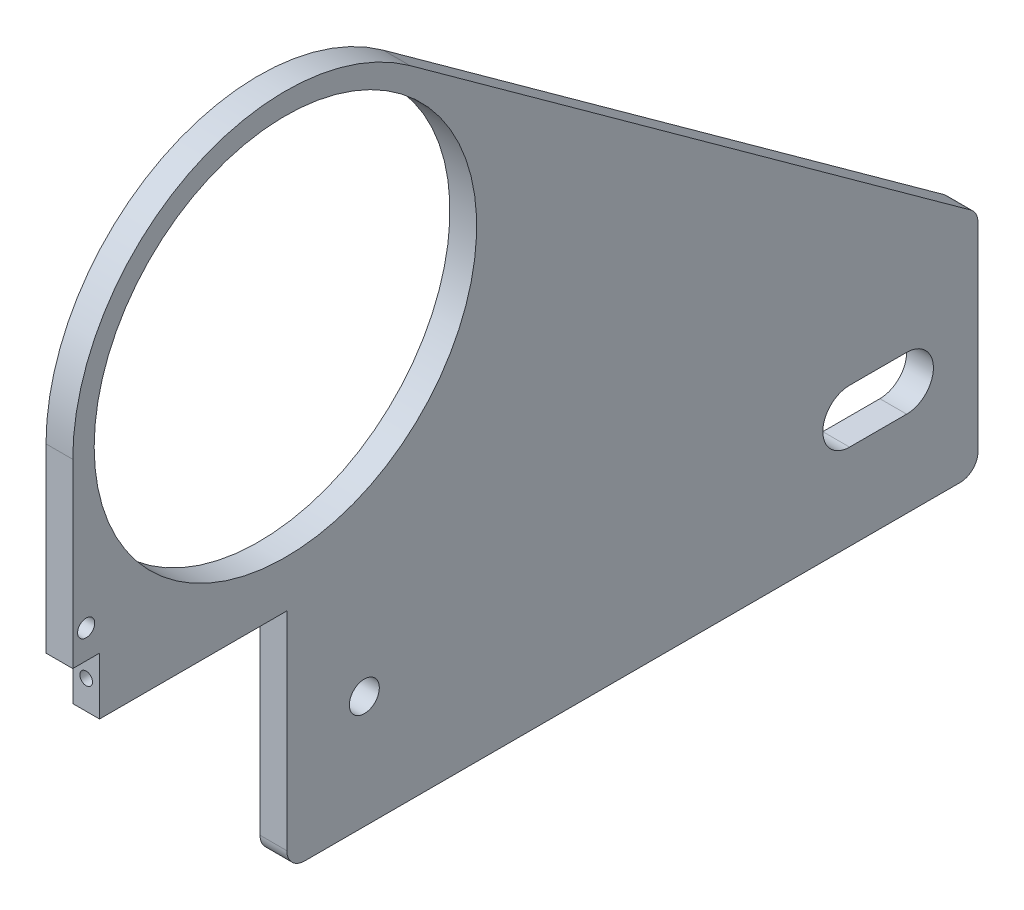
SolidWorks part; units mm, degrees
ref_plane "Front Plane" through (0, 0, 0) normal (0, 0, 1) x (1, 0, 0)
ref_plane "Top Plane" through (0, 0, 0) normal (0, 1, 0) x (1, 0, 0)
ref_plane "Right Plane" through (0, 0, 0) normal (1, 0, 0) x (0, 0, -1)
sketch "Sketch1" plane through (0, 0, 0) normal (1, 0, 0) x (0, 0, -1)
  line L0 (-39.2828, 0) -> (77.3828, 0)
  line L1 (80.5578, 3.175) -> (80.5578, 38.5097)
  line L2 (-80.5578, 82.55) -> (-80.5578, 50.292)
  line L3 (79.2431, 41.0826) -> (-20.5306, 113.2224)
  line L4 (-75.7953, 50.292) -> (-75.7953, 40.132)
  line L5 (67.8578, 20.066) -> (57.6978, 20.066) construction
  line L6 (67.8578, 15.3035) -> (57.6978, 15.3035)
  line L7 (-75.7953, 40.132) -> (-42.4578, 40.132)
  line L10 (-42.4578, 40.132) -> (-42.4578, 3.175)
  line L11 (-80.5578, 50.292) -> (-75.7953, 50.292)
  line L12 (67.8578, 24.8285) -> (57.6978, 24.8285)
  arc A0 (67.8578, 15.3035) -> (67.8578, 24.8285) centre (67.8578, 20.066) ccw
  circle A1 centre (-42.7078, 82.55) radius 31.5 construction
  circle A2 centre (67.8578, 20.066) radius 76.2 construction
  circle A3 centre (-78.1765, 55.372) radius 1.524
  arc A4 (57.6978, 24.8285) -> (57.6978, 15.3035) centre (57.6978, 20.066) ccw
  arc A5 (-20.5306, 113.2224) -> (-80.5578, 82.55) centre (-42.7078, 82.55) ccw
  arc A6 (-39.2828, 0) -> (-42.4578, 3.175) centre (-39.2828, 3.175) cw
  arc A7 (77.3828, 0) -> (80.5578, 3.175) centre (77.3828, 3.175) ccw
  arc A8 (80.5578, 38.5097) -> (79.2431, 41.0826) centre (77.3828, 38.5097) ccw
  circle A11 centre (-28.6622, 20.066) radius 2.667
  circle A16 centre (-42.7078, 82.55) radius 34.04
  point P8 (80.5578, 20.8423)
  point P10 (-42.4578, 21.6535)
  point P13 (62.7778, 20.066)
  point P28 (80.5578, 40.132)
  dimension "D4" = 9.525
  dimension "D7" = 4.7625
  dimension "D8" = 63
  dimension "D9" = 6.35
  dimension "D12" = 3.175
  dimension "D14" = 2.54
  dimension "D15" = 152.4
  dimension "D18" = 5.334
  dimension "D19" = 5.08
  dimension "D17" = 3.048
  dimension "D2" = 40.132
  dimension "D3" = 20.066
  dimension "D5" = 12.7
  dimension "D6" = 33.3375
  dimension "D10" = 127
  dimension "D11" = 109.22
  dimension "D21" = 10.16
  dimension "D22" = 10.16
  dimension "D16" = 2.3813
extrude "Boss-Extrude1" add sketch "Sketch1" along normal blind 4.7625
sketch "Sketch2" plane through (0, 0, 75.7953) normal (0, 0, 1) x (1, 0, 0)
  line L0 (0, 50.292) -> (0, 40.132) construction
  line L1 (4.7625, 40.132) -> (0, 40.132) construction
  circle A0 centre (2.3813, 45.212) radius 1.1303
  point P4 (0, 45.212)
  point P7 (2.3813, 40.132)
  dimension "D1" = 2.2606
extrude "Cut-Extrude1" cut sketch "Sketch2" against normal blind 6.35
